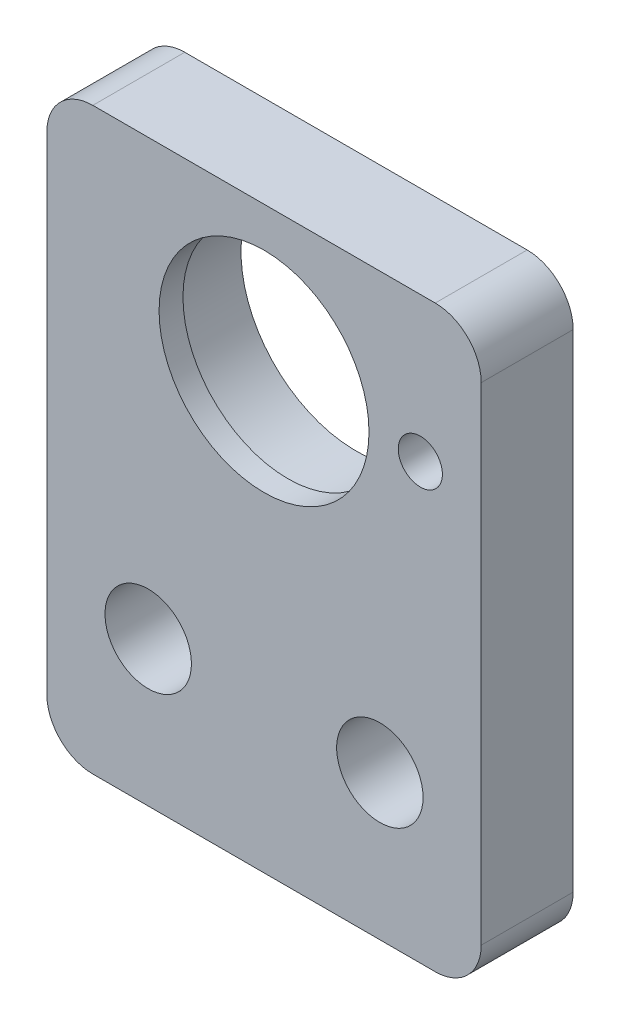
SolidWorks part; units mm, degrees
ref_plane "Front Plane" through (0, 0, 0) normal (0, 0, 1) x (1, 0, 0)
ref_plane "Top Plane" through (0, 0, 0) normal (0, 1, 0) x (1, 0, 0)
ref_plane "Right Plane" through (0, 0, 0) normal (1, 0, 0) x (0, 0, -1)
sketch "Sketch1" plane through (0, 0, 0) normal (0, 0, 1) x (1, 0, 0)
  line L5 (127.9917, 205.8589) -> (127.9917, 172.2089)
  line L6 (157.9917, 172.2089) -> (157.9917, 205.8589)
  line L15 (131.1667, 169.0339) -> (154.8167, 169.0339)
  line L42 (154.8167, 209.0339) -> (131.1667, 209.0339)
  circle A1 centre (142.9917, 199.0339) radius 7.9375
  circle A3 centre (142.9917, 199.0339) radius 7.25
  arc A6 (154.8167, 169.0339) -> (157.9917, 172.2089) centre (154.8167, 172.2089) ccw
  arc A7 (127.9917, 172.2089) -> (131.1667, 169.0339) centre (131.1667, 172.2089) ccw
  circle A10 centre (150.9917, 179.0339) radius 2.9845
  circle A11 centre (134.9917, 179.0339) radius 2.9845
  circle A13 centre (153.7867, 199.0339) radius 1.524
  arc A18 (131.1667, 209.0339) -> (127.9917, 205.8589) centre (131.1667, 205.8589) ccw
  arc A19 (157.9917, 205.8589) -> (154.8167, 209.0339) centre (154.8167, 205.8589) ccw
extrude "Boss-Extrude1" add sketch "Sketch1" along normal blind 6.35 contours L6 A19 L42 A18 L5 A7 L15 A6 A1 A10 A11 A13 | A1 A3 region at (142.907, 187.4291, 0) region at (135.2787, 199.0339, 0)
extrude "Cut-Extrude1" cut sketch "Sketch1<3>" along normal blind 4.699 contours A1 A3 region at (135.2787, 199.0339, 0)
sketch "Sketch1<3>" plane through (0, 0, 0) normal (0, 0, 1) x (1, 0, 0) same geometry as "Sketch1"
